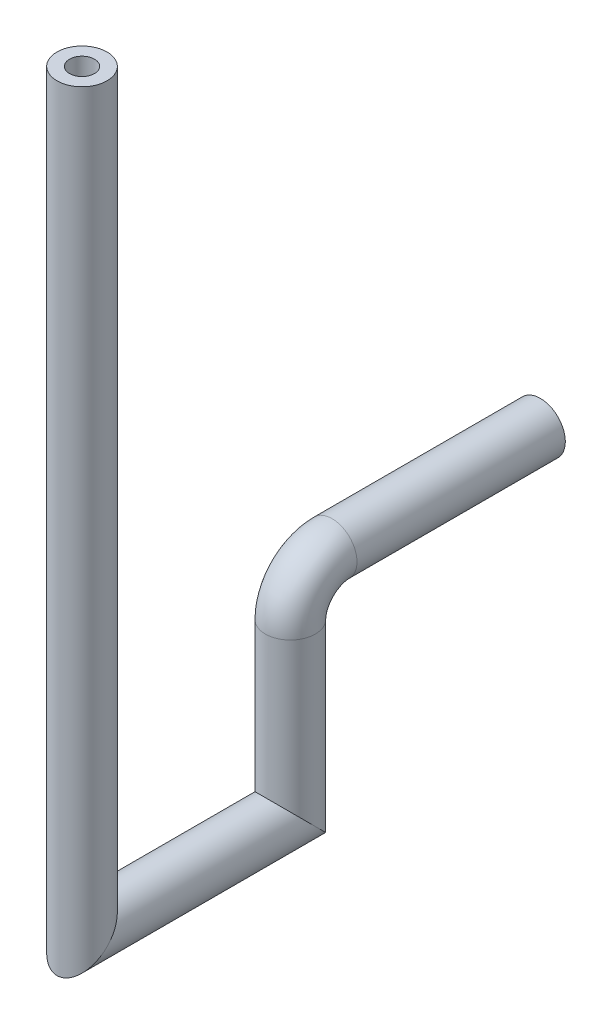
SolidWorks part; units mm, degrees
ref_plane "Plano frontal" through (0, 0, 0) normal (0, 0, 1) x (1, 0, 0)
ref_plane "Plano superior" through (0, 0, 0) normal (0, 1, 0) x (1, 0, 0)
ref_plane "Plano direito" through (0, 0, 0) normal (1, 0, 0) x (0, 0, -1)
sketch "Esboço1" plane through (0, 0, 0) normal (0, 0, 1) x (1, 0, 0)
  circle A0 centre (0, 0) radius 6
  circle A1 centre (0, 0) radius 3.5
extrude "Ressalto-extrusão1" add sketch "Esboço1" along normal blind 15
ref_plane "Plano1" through (0, 0, 15) normal (0, 0, 1) x (1, 0, 0)
sketch "Esboço2" plane through (0, 0, 15) normal (0, 0, 1) x (1, 0, 0)
  circle A0 centre (0, 0) radius 6
  circle A1 centre (0, 0) radius 3
extrude "Ressalto-extrusão2" add sketch "Esboço2" along normal blind 30
ref_plane "Plano2" through (0, 0, 45) normal (0, 0, 1) x (1, 0, 0)
sketch "Esboço3" plane through (0, 0, 45) normal (0, 0, 1) x (1, 0, 0)
  line L0 (0, -6) -> (0, 6)
  line L1 (6, 0) -> (-6, 0)
  line L2 (-6, -6) -> (6, -6)
  line L3 (-6, 0) -> (-6, -6)
  circle A0 centre (0, 0) radius 6 construction
ref_plane "Plano3" through (0, 0, 0) normal (1, 0, 0) x (0, 1, 0)
sketch "Esboço4" plane through (0, 0, 0) normal (1, 0, 0) x (0, 1, 0)
  line L0 (0, 45) -> (0, 50)
  line L1 (-6, 45) -> (6, 45) construction
  line L2 (-10, 60) -> (-50, 60)
  line L3 (-50, 60) -> (-50, 110)
  line L4 (-50, 110) -> (130, 110)
  arc A0 (-10, 60) -> (0, 50) centre (-10, 50) cw
  point P10 (0, 60)
  dimension "D2" = 10
  dimension "D1" = 15
sweep "Varredura-Fino1" add path "Esboço4" circular profile diameter 6 parameters "D1"=3, "D3"=6
ref_plane "Plano4" through (0, -6, 0) normal (0, 1, 0) x (1, 0, 0)
ref_plane "Plano5" through (0, -31, 0) normal (0, 1, 0) x (1, 0, 0)
ref_plane "Plano6" through (-6, 0, 0) normal (1, 0, 0) x (0, 0, -1)
sketch "Esboço118" plane through (0, -31, 0) normal (0, 1, 0) x (1, 0, 0)
  line L0 (-6, -60) -> (-6, -110)
  circle A0 centre (0, -110) radius 6 construction
sketch "Esboço114" plane through (-6, -37, 0) normal (1, 0, 0) x (0, -1, 0)
  line L0 (-6, -60) -> (-6, -84.5643) construction
  line L1 (-6, -60) -> (-6, -45.5701) construction
  line L2 (-6, -110) -> (-6, -131.4212) construction
  line L3 (-6.25, -60) -> (-6.25, -45.5701)
  line L4 (-6.25, -60) -> (-6.25, -84.5643)
  line L5 (-6.25, -110) -> (-6.25, -131.4212)
  line L6 (-5.75, -60) -> (-5.75, -45.5701)
  line L7 (-5.75, -60) -> (-5.75, -84.5643)
  line L8 (-5.75, -110) -> (-5.75, -131.4212)
  line L9 (-6.25, -45.5701) -> (-5.75, -45.5701)
  line L10 (-6.25, -131.4212) -> (-5.75, -131.4212)
  line L11 (-6.25, -84.5643) -> (-5.75, -84.5643)
  line L12 (-6.25, -90.4498) -> (-5.75, -90.4498)
  line L13 (-6.25, -90.4498) -> (-6.25, -110)
  line L14 (-6.25, -60) -> (-6.25, -110) construction
  line L15 (-6, -90.4498) -> (-6, -110) construction
  line L16 (-6, -60) -> (-6, -110) construction
  line L17 (-5.75, -90.4498) -> (-5.75, -110)
  line L18 (-5.75, -60) -> (-5.75, -110) construction
  line L19 (-6, -85) -> (-0.4218, -85) construction
  line L20 (-6, -60) -> (-6, -110) construction
  line L21 (-16.25, -90.4498) -> (-16.25, -110)
  line L22 (-15.75, -90.4498) -> (-15.75, -110)
  line L23 (-16.25, -90.4498) -> (-15.75, -90.4498)
  line L24 (-15.75, -110) -> (-15.75, -131.4212)
  line L25 (-16.25, -110) -> (-16.25, -131.4212)
  line L26 (-16.25, -131.4212) -> (-15.75, -131.4212)
  line L27 (-26.25, -90.4498) -> (-26.25, -110)
  line L28 (-25.75, -90.4498) -> (-25.75, -110)
  line L29 (-26.25, -90.4498) -> (-25.75, -90.4498)
  line L30 (-25.75, -110) -> (-25.75, -131.4212)
  line L31 (-26.25, -110) -> (-26.25, -131.4212)
  line L32 (-26.25, -131.4212) -> (-25.75, -131.4212)
  line L33 (-36.25, -90.4498) -> (-36.25, -110)
  line L34 (-35.75, -90.4498) -> (-35.75, -110)
  line L35 (-36.25, -90.4498) -> (-35.75, -90.4498)
  line L36 (-35.75, -110) -> (-35.75, -131.4212)
  line L37 (-36.25, -110) -> (-36.25, -131.4212)
  line L38 (-36.25, -131.4212) -> (-35.75, -131.4212)
  line L39 (-46.25, -90.4498) -> (-46.25, -110)
  line L40 (-45.75, -90.4498) -> (-45.75, -110)
  line L41 (-46.25, -90.4498) -> (-45.75, -90.4498)
  line L42 (-45.75, -110) -> (-45.75, -131.4212)
  line L43 (-46.25, -110) -> (-46.25, -131.4212)
  line L44 (-46.25, -131.4212) -> (-45.75, -131.4212)
  line L45 (-56.25, -90.4498) -> (-56.25, -110)
  line L46 (-55.75, -90.4498) -> (-55.75, -110)
  line L47 (-56.25, -90.4498) -> (-55.75, -90.4498)
  line L48 (-55.75, -110) -> (-55.75, -131.4212)
  line L49 (-56.25, -110) -> (-56.25, -131.4212)
  line L50 (-56.25, -131.4212) -> (-55.75, -131.4212)
  line L51 (-66.25, -90.4498) -> (-66.25, -110)
  line L52 (-65.75, -90.4498) -> (-65.75, -110)
  line L53 (-66.25, -90.4498) -> (-65.75, -90.4498)
  line L54 (-65.75, -110) -> (-65.75, -131.4212)
  line L55 (-66.25, -110) -> (-66.25, -131.4212)
  line L56 (-66.25, -131.4212) -> (-65.75, -131.4212)
  line L57 (-76.25, -90.4498) -> (-76.25, -110)
  line L58 (-75.75, -90.4498) -> (-75.75, -110)
  line L59 (-76.25, -90.4498) -> (-75.75, -90.4498)
  line L60 (-75.75, -110) -> (-75.75, -131.4212)
  line L61 (-76.25, -110) -> (-76.25, -131.4212)
  line L62 (-76.25, -131.4212) -> (-75.75, -131.4212)
  line L63 (-86.25, -90.4498) -> (-86.25, -110)
  line L64 (-85.75, -90.4498) -> (-85.75, -110)
  line L65 (-86.25, -90.4498) -> (-85.75, -90.4498)
  line L66 (-85.75, -110) -> (-85.75, -131.4212)
  line L67 (-86.25, -110) -> (-86.25, -131.4212)
  line L68 (-86.25, -131.4212) -> (-85.75, -131.4212)
  line L69 (-96.25, -90.4498) -> (-96.25, -110)
  line L70 (-95.75, -90.4498) -> (-95.75, -110)
  line L71 (-96.25, -90.4498) -> (-95.75, -90.4498)
  line L72 (-95.75, -110) -> (-95.75, -131.4212)
  line L73 (-96.25, -110) -> (-96.25, -131.4212)
  line L74 (-96.25, -131.4212) -> (-95.75, -131.4212)
  line L75 (-106.25, -90.4498) -> (-105.75, -90.4498)
  line L76 (-106.25, -90.4498) -> (-106.25, -110)
  line L83 (-105.75, -90.4498) -> (-105.75, -110)
  line L84 (-105.75, -110) -> (-105.75, -131.4212)
  line L85 (-106.25, -110) -> (-106.25, -131.4212)
  line L86 (-106.25, -131.4212) -> (-105.75, -131.4212)
  dimension "D4" = 2
  dimension "D1" = 0.25
  dimension "D2" = 0.25
  dimension "D3" = 10
extrude "Corte-extrusão2" cut sketch "Esboço114" along normal blind 1
ref_plane "Plano8" through (-6, 0, 0) normal (1, 0, 0) x (0, 0, -1)
sketch "Esboço119" plane through (-6, 0, 0) normal (1, 0, 0) x (0, 0, -1)
  line L0 (-108, -31.25) -> (-112, -31.25)
  line L2 (-108, -30.75) -> (-112, -30.75)
  line L3 (-112, -31.25) -> (-112, -30.75)
  line L4 (-110, -30.75) -> (-110, -31.25) construction
  line L5 (-108, -30.75) -> (-108, -31.25)
  line L6 (-112, -30.75) -> (-112, -31.25)
  line L7 (-108, -29.75) -> (-108, -30.25)
  line L8 (-108, -29.75) -> (-112, -29.75)
  line L9 (-112, -30.25) -> (-112, -29.75)
  line L10 (-108, -30.25) -> (-112, -30.25)
  line L11 (-108, -28.75) -> (-108, -29.25)
  line L12 (-108, -28.75) -> (-112, -28.75)
  line L13 (-112, -29.25) -> (-112, -28.75)
  line L14 (-108, -29.25) -> (-112, -29.25)
  line L15 (-108, -27.75) -> (-108, -28.25)
  line L16 (-108, -27.75) -> (-112, -27.75)
  line L17 (-112, -28.25) -> (-112, -27.75)
  line L18 (-108, -28.25) -> (-112, -28.25)
  line L19 (-108, -26.75) -> (-108, -27.25)
  line L20 (-108, -26.75) -> (-112, -26.75)
  line L21 (-112, -27.25) -> (-112, -26.75)
  line L22 (-108, -27.25) -> (-112, -27.25)
  line L23 (-108, -25.75) -> (-108, -26.25)
  line L24 (-108, -25.75) -> (-112, -25.75)
  line L25 (-112, -26.25) -> (-112, -25.75)
  line L26 (-108, -26.25) -> (-112, -26.25)
  line L27 (-108, -24.75) -> (-108, -25.25)
  line L28 (-108, -24.75) -> (-112, -24.75)
  line L29 (-112, -25.25) -> (-112, -24.75)
  line L30 (-108, -25.25) -> (-112, -25.25)
  line L31 (-108, -23.75) -> (-108, -24.25)
  line L32 (-108, -23.75) -> (-112, -23.75)
  line L33 (-112, -24.25) -> (-112, -23.75)
  line L34 (-108, -24.25) -> (-112, -24.25)
  line L35 (-108, -22.75) -> (-108, -23.25)
  line L36 (-108, -22.75) -> (-112, -22.75)
  line L37 (-112, -23.25) -> (-112, -22.75)
  line L38 (-108, -23.25) -> (-112, -23.25)
  line L39 (-108, -21.75) -> (-108, -22.25)
  line L40 (-108, -21.75) -> (-112, -21.75)
  line L41 (-112, -22.25) -> (-112, -21.75)
  line L42 (-108, -22.25) -> (-112, -22.25)
  line L43 (-108, -20.75) -> (-108, -21.25)
  line L44 (-108, -20.75) -> (-112, -20.75)
  line L45 (-112, -21.25) -> (-112, -20.75)
  line L46 (-108, -21.25) -> (-112, -21.25)
  line L47 (-108, -19.75) -> (-108, -20.25)
  line L48 (-108, -19.75) -> (-112, -19.75)
  line L49 (-112, -20.25) -> (-112, -19.75)
  line L50 (-108, -20.25) -> (-112, -20.25)
  line L51 (-108, -18.75) -> (-108, -19.25)
  line L52 (-108, -18.75) -> (-112, -18.75)
  line L53 (-112, -19.25) -> (-112, -18.75)
  line L54 (-108, -19.25) -> (-112, -19.25)
  line L55 (-108, -17.75) -> (-108, -18.25)
  line L56 (-108, -17.75) -> (-112, -17.75)
  line L57 (-112, -18.25) -> (-112, -17.75)
  line L58 (-108, -18.25) -> (-112, -18.25)
  line L59 (-108, -16.75) -> (-108, -17.25)
  line L60 (-108, -16.75) -> (-112, -16.75)
  line L61 (-112, -17.25) -> (-112, -16.75)
  line L62 (-108, -17.25) -> (-112, -17.25)
  line L63 (-108, -15.75) -> (-108, -16.25)
  line L64 (-108, -15.75) -> (-112, -15.75)
  line L65 (-112, -16.25) -> (-112, -15.75)
  line L66 (-108, -16.25) -> (-112, -16.25)
  line L67 (-108, -14.75) -> (-108, -15.25)
  line L68 (-108, -14.75) -> (-112, -14.75)
  line L69 (-112, -15.25) -> (-112, -14.75)
  line L70 (-108, -15.25) -> (-112, -15.25)
  line L71 (-108, -13.75) -> (-108, -14.25)
  line L72 (-108, -13.75) -> (-112, -13.75)
  line L73 (-112, -14.25) -> (-112, -13.75)
  line L74 (-108, -14.25) -> (-112, -14.25)
  line L75 (-108, -12.75) -> (-108, -13.25)
  line L76 (-108, -12.75) -> (-112, -12.75)
  line L77 (-112, -13.25) -> (-112, -12.75)
  line L78 (-108, -13.25) -> (-112, -13.25)
  line L79 (-108, -11.75) -> (-108, -12.25)
  line L80 (-108, -11.75) -> (-112, -11.75)
  line L81 (-112, -12.25) -> (-112, -11.75)
  line L82 (-108, -12.25) -> (-112, -12.25)
  line L83 (-108, -10.75) -> (-108, -11.25)
  line L84 (-108, -10.75) -> (-112, -10.75)
  line L85 (-112, -11.25) -> (-112, -10.75)
  line L86 (-108, -11.25) -> (-112, -11.25)
  line L87 (-108, -9.75) -> (-108, -10.25)
  line L88 (-108, -9.75) -> (-112, -9.75)
  line L89 (-112, -10.25) -> (-112, -9.75)
  line L90 (-108, -10.25) -> (-112, -10.25)
  line L91 (-108, -8.75) -> (-108, -9.25)
  line L92 (-108, -8.75) -> (-112, -8.75)
  line L93 (-112, -9.25) -> (-112, -8.75)
  line L94 (-108, -9.25) -> (-112, -9.25)
  line L95 (-108, -7.75) -> (-108, -8.25)
  line L96 (-108, -7.75) -> (-112, -7.75)
  line L97 (-112, -8.25) -> (-112, -7.75)
  line L98 (-108, -8.25) -> (-112, -8.25)
  line L99 (-108, -6.75) -> (-108, -7.25)
  line L100 (-108, -6.75) -> (-112, -6.75)
  line L101 (-112, -7.25) -> (-112, -6.75)
  line L102 (-108, -7.25) -> (-112, -7.25)
  line L103 (-108, -5.75) -> (-108, -6.25)
  line L104 (-108, -5.75) -> (-112, -5.75)
  line L105 (-112, -6.25) -> (-112, -5.75)
  line L106 (-108, -6.25) -> (-112, -6.25)
  line L107 (-108, -4.75) -> (-108, -5.25)
  line L108 (-108, -4.75) -> (-112, -4.75)
  line L109 (-112, -5.25) -> (-112, -4.75)
  line L110 (-108, -5.25) -> (-112, -5.25)
  line L111 (-108, -3.75) -> (-108, -4.25)
  line L112 (-108, -3.75) -> (-112, -3.75)
  line L113 (-112, -4.25) -> (-112, -3.75)
  line L114 (-108, -4.25) -> (-112, -4.25)
  line L115 (-108, -2.75) -> (-108, -3.25)
  line L116 (-108, -2.75) -> (-112, -2.75)
  line L117 (-112, -3.25) -> (-112, -2.75)
  line L118 (-108, -3.25) -> (-112, -3.25)
  line L119 (-108, -1.75) -> (-108, -2.25)
  line L120 (-108, -1.75) -> (-112, -1.75)
  line L121 (-112, -2.25) -> (-112, -1.75)
  line L122 (-108, -2.25) -> (-112, -2.25)
  line L123 (-108, -0.75) -> (-108, -1.25)
  line L124 (-108, -0.75) -> (-112, -0.75)
  line L125 (-112, -1.25) -> (-112, -0.75)
  line L126 (-108, -1.25) -> (-112, -1.25)
  line L127 (-108, 0.25) -> (-108, -0.25)
  line L128 (-108, 0.25) -> (-112, 0.25)
  line L129 (-112, -0.25) -> (-112, 0.25)
  line L130 (-108, -0.25) -> (-112, -0.25)
  line L131 (-108, 1.25) -> (-108, 0.75)
  line L132 (-108, 1.25) -> (-112, 1.25)
  line L133 (-112, 0.75) -> (-112, 1.25)
  line L134 (-108, 0.75) -> (-112, 0.75)
  line L135 (-108, 2.25) -> (-108, 1.75)
  line L136 (-108, 2.25) -> (-112, 2.25)
  line L137 (-112, 1.75) -> (-112, 2.25)
  line L138 (-108, 1.75) -> (-112, 1.75)
  line L139 (-108, 3.25) -> (-108, 2.75)
  line L140 (-108, 3.25) -> (-112, 3.25)
  line L141 (-112, 2.75) -> (-112, 3.25)
  line L142 (-108, 2.75) -> (-112, 2.75)
  line L143 (-108, 4.25) -> (-108, 3.75)
  line L144 (-108, 4.25) -> (-112, 4.25)
  line L145 (-112, 3.75) -> (-112, 4.25)
  line L146 (-108, 3.75) -> (-112, 3.75)
  line L147 (-108, 5.25) -> (-108, 4.75)
  line L148 (-108, 5.25) -> (-112, 5.25)
  line L149 (-112, 4.75) -> (-112, 5.25)
  line L150 (-108, 4.75) -> (-112, 4.75)
  line L151 (-108, 6.25) -> (-108, 5.75)
  line L152 (-108, 6.25) -> (-112, 6.25)
  line L153 (-112, 5.75) -> (-112, 6.25)
  line L154 (-108, 5.75) -> (-112, 5.75)
  line L155 (-108, 7.25) -> (-108, 6.75)
  line L156 (-108, 7.25) -> (-112, 7.25)
  line L157 (-112, 6.75) -> (-112, 7.25)
  line L158 (-108, 6.75) -> (-112, 6.75)
  line L159 (-108, 8.25) -> (-108, 7.75)
  line L160 (-108, 8.25) -> (-112, 8.25)
  line L161 (-112, 7.75) -> (-112, 8.25)
  line L162 (-108, 7.75) -> (-112, 7.75)
  line L163 (-108, 9.25) -> (-108, 8.75)
  line L164 (-108, 9.25) -> (-112, 9.25)
  line L165 (-112, 8.75) -> (-112, 9.25)
  line L166 (-108, 8.75) -> (-112, 8.75)
  line L167 (-108, 10.25) -> (-108, 9.75)
  line L168 (-108, 10.25) -> (-112, 10.25)
  line L169 (-112, 9.75) -> (-112, 10.25)
  line L170 (-108, 9.75) -> (-112, 9.75)
  line L171 (-108, 11.25) -> (-108, 10.75)
  line L172 (-108, 11.25) -> (-112, 11.25)
  line L173 (-112, 10.75) -> (-112, 11.25)
  line L174 (-108, 10.75) -> (-112, 10.75)
  line L175 (-108, 12.25) -> (-108, 11.75)
  line L176 (-108, 12.25) -> (-112, 12.25)
  line L177 (-112, 11.75) -> (-112, 12.25)
  line L178 (-108, 11.75) -> (-112, 11.75)
  line L179 (-108, 13.25) -> (-108, 12.75)
  line L180 (-108, 13.25) -> (-112, 13.25)
  line L181 (-112, 12.75) -> (-112, 13.25)
  line L182 (-108, 12.75) -> (-112, 12.75)
  line L183 (-108, 14.25) -> (-108, 13.75)
  line L184 (-108, 14.25) -> (-112, 14.25)
  line L185 (-112, 13.75) -> (-112, 14.25)
  line L186 (-108, 13.75) -> (-112, 13.75)
  line L187 (-108, 15.25) -> (-108, 14.75)
  line L188 (-108, 15.25) -> (-112, 15.25)
  line L189 (-112, 14.75) -> (-112, 15.25)
  line L190 (-108, 14.75) -> (-112, 14.75)
  line L191 (-108, 16.25) -> (-108, 15.75)
  line L192 (-108, 16.25) -> (-112, 16.25)
  line L193 (-112, 15.75) -> (-112, 16.25)
  line L194 (-108, 15.75) -> (-112, 15.75)
  line L195 (-108, 17.25) -> (-108, 16.75)
  line L196 (-108, 17.25) -> (-112, 17.25)
  line L197 (-112, 16.75) -> (-112, 17.25)
  line L198 (-108, 16.75) -> (-112, 16.75)
  line L199 (-108, 18.25) -> (-108, 17.75)
  line L200 (-108, 18.25) -> (-112, 18.25)
  line L201 (-112, 17.75) -> (-112, 18.25)
  line L202 (-108, 17.75) -> (-112, 17.75)
  line L203 (-108, 19.25) -> (-108, 18.75)
  line L204 (-108, 19.25) -> (-112, 19.25)
  line L205 (-112, 18.75) -> (-112, 19.25)
  line L206 (-108, 18.75) -> (-112, 18.75)
  line L207 (-108, 20.25) -> (-108, 19.75)
  line L208 (-108, 20.25) -> (-112, 20.25)
  line L209 (-112, 19.75) -> (-112, 20.25)
  line L210 (-108, 19.75) -> (-112, 19.75)
  line L211 (-108, 21.25) -> (-108, 20.75)
  line L212 (-108, 21.25) -> (-112, 21.25)
  line L213 (-112, 20.75) -> (-112, 21.25)
  line L214 (-108, 20.75) -> (-112, 20.75)
  line L215 (-108, 22.25) -> (-108, 21.75)
  line L216 (-108, 22.25) -> (-112, 22.25)
  line L217 (-112, 21.75) -> (-112, 22.25)
  line L218 (-108, 21.75) -> (-112, 21.75)
  line L219 (-108, 23.25) -> (-108, 22.75)
  line L220 (-108, 23.25) -> (-112, 23.25)
  line L221 (-112, 22.75) -> (-112, 23.25)
  line L222 (-108, 22.75) -> (-112, 22.75)
  line L223 (-108, 24.25) -> (-108, 23.75)
  line L224 (-108, 24.25) -> (-112, 24.25)
  line L225 (-112, 23.75) -> (-112, 24.25)
  line L226 (-108, 23.75) -> (-112, 23.75)
  line L227 (-108, 25.25) -> (-108, 24.75)
  line L228 (-108, 25.25) -> (-112, 25.25)
  line L229 (-112, 24.75) -> (-112, 25.25)
  line L230 (-108, 24.75) -> (-112, 24.75)
  line L231 (-108, 26.25) -> (-108, 25.75)
  line L232 (-108, 26.25) -> (-112, 26.25)
  line L233 (-112, 25.75) -> (-112, 26.25)
  line L234 (-108, 25.75) -> (-112, 25.75)
  line L235 (-108, 27.25) -> (-108, 26.75)
  line L236 (-108, 27.25) -> (-112, 27.25)
  line L237 (-112, 26.75) -> (-112, 27.25)
  line L238 (-108, 26.75) -> (-112, 26.75)
  line L239 (-108, 28.25) -> (-108, 27.75)
  line L240 (-108, 28.25) -> (-112, 28.25)
  line L241 (-112, 27.75) -> (-112, 28.25)
  line L242 (-108, 27.75) -> (-112, 27.75)
  line L243 (-108, 29.25) -> (-108, 28.75)
  line L244 (-108, 29.25) -> (-112, 29.25)
  line L245 (-112, 28.75) -> (-112, 29.25)
  line L246 (-108, 28.75) -> (-112, 28.75)
  line L247 (-108, 30.25) -> (-108, 29.75)
  line L248 (-108, 30.25) -> (-112, 30.25)
  line L249 (-112, 29.75) -> (-112, 30.25)
  line L250 (-108, 29.75) -> (-112, 29.75)
  line L251 (-108, 31.25) -> (-108, 30.75)
  line L252 (-108, 31.25) -> (-112, 31.25)
  line L253 (-112, 30.75) -> (-112, 31.25)
  line L254 (-108, 30.75) -> (-112, 30.75)
  line L255 (-108, 32.25) -> (-108, 31.75)
  line L256 (-108, 32.25) -> (-112, 32.25)
  line L257 (-112, 31.75) -> (-112, 32.25)
  line L258 (-108, 31.75) -> (-112, 31.75)
  line L259 (-108, 33.25) -> (-108, 32.75)
  line L260 (-108, 33.25) -> (-112, 33.25)
  line L261 (-112, 32.75) -> (-112, 33.25)
  line L262 (-108, 32.75) -> (-112, 32.75)
  line L263 (-108, 34.25) -> (-108, 33.75)
  line L264 (-108, 34.25) -> (-112, 34.25)
  line L265 (-112, 33.75) -> (-112, 34.25)
  line L266 (-108, 33.75) -> (-112, 33.75)
  line L267 (-108, 35.25) -> (-108, 34.75)
  line L268 (-108, 35.25) -> (-112, 35.25)
  line L269 (-112, 34.75) -> (-112, 35.25)
  line L270 (-108, 34.75) -> (-112, 34.75)
  line L271 (-108, 36.25) -> (-108, 35.75)
  line L272 (-108, 36.25) -> (-112, 36.25)
  line L273 (-112, 35.75) -> (-112, 36.25)
  line L274 (-108, 35.75) -> (-112, 35.75)
  line L275 (-108, 37.25) -> (-108, 36.75)
  line L276 (-108, 37.25) -> (-112, 37.25)
  line L277 (-112, 36.75) -> (-112, 37.25)
  line L278 (-108, 36.75) -> (-112, 36.75)
  line L279 (-108, 38.25) -> (-108, 37.75)
  line L280 (-108, 38.25) -> (-112, 38.25)
  line L281 (-112, 37.75) -> (-112, 38.25)
  line L282 (-108, 37.75) -> (-112, 37.75)
  line L283 (-108, 39.25) -> (-108, 38.75)
  line L284 (-108, 39.25) -> (-112, 39.25)
  line L285 (-112, 38.75) -> (-112, 39.25)
  line L286 (-108, 38.75) -> (-112, 38.75)
  line L287 (-108, 40.25) -> (-108, 39.75)
  line L288 (-108, 40.25) -> (-112, 40.25)
  line L289 (-112, 39.75) -> (-112, 40.25)
  line L290 (-108, 39.75) -> (-112, 39.75)
  line L291 (-108, 41.25) -> (-108, 40.75)
  line L292 (-108, 41.25) -> (-112, 41.25)
  line L293 (-112, 40.75) -> (-112, 41.25)
  line L294 (-108, 40.75) -> (-112, 40.75)
  line L295 (-108, 42.25) -> (-108, 41.75)
  line L296 (-108, 42.25) -> (-112, 42.25)
  line L297 (-112, 41.75) -> (-112, 42.25)
  line L298 (-108, 41.75) -> (-112, 41.75)
  line L299 (-108, 43.25) -> (-108, 42.75)
  line L300 (-108, 43.25) -> (-112, 43.25)
  line L301 (-112, 42.75) -> (-112, 43.25)
  line L302 (-108, 42.75) -> (-112, 42.75)
  line L303 (-108, 44.25) -> (-108, 43.75)
  line L304 (-108, 44.25) -> (-112, 44.25)
  line L305 (-112, 43.75) -> (-112, 44.25)
  line L306 (-108, 43.75) -> (-112, 43.75)
  line L307 (-108, 45.25) -> (-108, 44.75)
  line L308 (-108, 45.25) -> (-112, 45.25)
  line L309 (-112, 44.75) -> (-112, 45.25)
  line L310 (-108, 44.75) -> (-112, 44.75)
  line L311 (-108, 46.25) -> (-108, 45.75)
  line L312 (-108, 46.25) -> (-112, 46.25)
  line L313 (-112, 45.75) -> (-112, 46.25)
  line L314 (-108, 45.75) -> (-112, 45.75)
  line L315 (-108, 47.25) -> (-108, 46.75)
  line L316 (-108, 47.25) -> (-112, 47.25)
  line L317 (-112, 46.75) -> (-112, 47.25)
  line L318 (-108, 46.75) -> (-112, 46.75)
  line L319 (-108, 48.25) -> (-108, 47.75)
  line L320 (-108, 48.25) -> (-112, 48.25)
  line L321 (-112, 47.75) -> (-112, 48.25)
  line L322 (-108, 47.75) -> (-112, 47.75)
  line L323 (-108, 49.25) -> (-108, 48.75)
  line L324 (-108, 49.25) -> (-112, 49.25)
  line L325 (-112, 48.75) -> (-112, 49.25)
  line L326 (-108, 48.75) -> (-112, 48.75)
  line L327 (-108, 50.25) -> (-108, 49.75)
  line L328 (-108, 50.25) -> (-112, 50.25)
  line L329 (-112, 49.75) -> (-112, 50.25)
  line L330 (-108, 49.75) -> (-112, 49.75)
  line L331 (-108, 51.25) -> (-108, 50.75)
  line L332 (-108, 51.25) -> (-112, 51.25)
  line L333 (-112, 50.75) -> (-112, 51.25)
  line L334 (-108, 50.75) -> (-112, 50.75)
  line L335 (-108, 52.25) -> (-108, 51.75)
  line L336 (-108, 52.25) -> (-112, 52.25)
  line L337 (-112, 51.75) -> (-112, 52.25)
  line L338 (-108, 51.75) -> (-112, 51.75)
  line L339 (-108, 53.25) -> (-108, 52.75)
  line L340 (-108, 53.25) -> (-112, 53.25)
  line L341 (-112, 52.75) -> (-112, 53.25)
  line L342 (-108, 52.75) -> (-112, 52.75)
  line L343 (-108, 54.25) -> (-108, 53.75)
  line L344 (-108, 54.25) -> (-112, 54.25)
  line L345 (-112, 53.75) -> (-112, 54.25)
  line L346 (-108, 53.75) -> (-112, 53.75)
  line L347 (-108, 55.25) -> (-108, 54.75)
  line L348 (-108, 55.25) -> (-112, 55.25)
  line L349 (-112, 54.75) -> (-112, 55.25)
  line L350 (-108, 54.75) -> (-112, 54.75)
  line L351 (-108, 56.25) -> (-108, 55.75)
  line L352 (-108, 56.25) -> (-112, 56.25)
  line L353 (-112, 55.75) -> (-112, 56.25)
  line L354 (-108, 55.75) -> (-112, 55.75)
  line L355 (-108, 57.25) -> (-108, 56.75)
  line L356 (-108, 57.25) -> (-112, 57.25)
  line L357 (-112, 56.75) -> (-112, 57.25)
  line L358 (-108, 56.75) -> (-112, 56.75)
  line L359 (-108, 58.25) -> (-108, 57.75)
  line L360 (-108, 58.25) -> (-112, 58.25)
  line L361 (-112, 57.75) -> (-112, 58.25)
  line L362 (-108, 57.75) -> (-112, 57.75)
  line L363 (-108, 59.25) -> (-108, 58.75)
  line L364 (-108, 59.25) -> (-112, 59.25)
  line L365 (-112, 58.75) -> (-112, 59.25)
  line L366 (-108, 58.75) -> (-112, 58.75)
  line L367 (-108, 59.75) -> (-112, 59.75)
  line L368 (-108, 60.25) -> (-112, 60.25)
  line L369 (-108, 60.25) -> (-108, 59.75)
  line L370 (-112, 59.75) -> (-112, 60.25)
  line L371 (-108, 60.75) -> (-112, 60.75)
  line L372 (-108, 61.25) -> (-112, 61.25)
  line L373 (-108, 61.25) -> (-108, 60.75)
  line L374 (-112, 60.75) -> (-112, 61.25)
  line L375 (-108, 61.75) -> (-112, 61.75)
  line L376 (-108, 62.25) -> (-112, 62.25)
  line L377 (-108, 62.25) -> (-108, 61.75)
  line L378 (-112, 61.75) -> (-112, 62.25)
  line L379 (-108, 62.75) -> (-112, 62.75)
  line L380 (-108, 63.25) -> (-112, 63.25)
  line L381 (-108, 63.25) -> (-108, 62.75)
  line L382 (-112, 62.75) -> (-112, 63.25)
  line L383 (-108, 63.75) -> (-112, 63.75)
  line L384 (-108, 64.25) -> (-112, 64.25)
  line L385 (-108, 64.25) -> (-108, 63.75)
  line L386 (-112, 63.75) -> (-112, 64.25)
  line L387 (-108, 64.75) -> (-112, 64.75)
  line L388 (-108, 65.25) -> (-112, 65.25)
  line L389 (-108, 65.25) -> (-108, 64.75)
  line L390 (-112, 64.75) -> (-112, 65.25)
  line L391 (-108, 65.75) -> (-112, 65.75)
  line L392 (-108, 66.25) -> (-112, 66.25)
  line L393 (-108, 66.25) -> (-108, 65.75)
  line L394 (-112, 65.75) -> (-112, 66.25)
  line L395 (-108, 66.75) -> (-112, 66.75)
  line L396 (-108, 67.25) -> (-112, 67.25)
  line L397 (-108, 67.25) -> (-108, 66.75)
  line L398 (-112, 66.75) -> (-112, 67.25)
  line L399 (-108, 67.75) -> (-112, 67.75)
  line L400 (-108, 68.25) -> (-112, 68.25)
  line L401 (-108, 68.25) -> (-108, 67.75)
  line L402 (-112, 67.75) -> (-112, 68.25)
  line L403 (-108, 68.75) -> (-112, 68.75)
  line L404 (-108, 69.25) -> (-112, 69.25)
  line L405 (-108, 69.25) -> (-108, 68.75)
  line L406 (-112, 68.75) -> (-112, 69.25)
  dimension "D1" = 91
  dimension "D2" = 2
  dimension "D3" = 2
  dimension "D4" = 11
extrude "Corte-extrusão3" cut sketch "Esboço119" along normal blind 0.5 contours L366 L363 L364 L365 | L362 L359 L360 L361 | L358 L355 L356 L357 | L354 L351 L352 L353 | L350 L347 L348 L349 | L346 L343 L344 L345 | L342 L339 L340 L341 | L338 L335 L336 L337 | L334 L331 L332 L333 | L330 L327 L328 L329 | L326 L323 L324 L325 | L322 L319 L320 L321 | L318 L315 L316 L317 | L314 L311 L312 L313 | L310 L307 L308 L309 | L306 L303 L304 L305 | L302 L299 L300 L301 | L298 L295 L296 L297 | L294 L291 L292 L293 | L290 L287 L288 L289 | L286 L283 L284 L285 | L282 L279 L280 L281 | L278 L275 L276 L277 | L274 L271 L272 L273 | L270 L267 L268 L269 | L266 L263 L264 L265 | L262 L259 L260 L261 | L258 L255 L256 L257 | L254 L251 L252 L253 | L250 L247 L248 L249 | L246 L243 L244 L245 | L242 L239 L240 L241 | L238 L235 L236 L237 | L234 L231 L232 L233 | L230 L227 L228 L229 | L226 L223 L224 L225 | L222 L219 L220 L221 | L218 L215 L216 L217 | L214 L211 L212 L213 | L210 L207 L208 L209 | L206 L203 L204 L205 | L202 L199 L200 L201 | L198 L195 L196 L197 | L194 L191 L192 L193 | L190 L187 L188 L189 | L186 L183 L184 L185 | L182 L179 L180 L181 | L178 L175 L176 L177 | L174 L171 L172 L173 | L170 L167 L168 L169 | L166 L163 L164 L165 | L162 L159 L160 L161 | L158 L155 L156 L157 | L154 L151 L152 L153 | L150 L147 L148 L149 | L142 L139 L140 L141 | L138 L135 L136 L137 | L134 L131 L132 L133 | L130 L127 L128 L129 | L126 L123 L124 L125 | L122 L119 L120 L121 | L118 L115 L116 L117 | L114 L111 L112 L113 | L110 L107 L108 L109 | L106 L103 L104 L105 | L102 L99 L100 L101 | L98 L95 L96 L97 | L94 L91 L92 L93 | L90 L87 L88 L89 | L82 L79 L80 L81 | L78 L75 L76 L77 | L74 L71 L72 L73 | L70 L67 L68 L69 | L66 L63 L64 L65 | L62 L59 L60 L61 | L58 L55 L56 L57 | L54 L51 L52 L53 | L50 L47 L48 L49 | L46 L43 L44 L45 | L42 L39 L40 L41 | L38 L35 L36 L37 | L34 L31 L32 L33 | L30 L27 L28 L29 | L26 L23 L24 L25 | L22 L19 L20 L21 | L18 L15 L16 L17 | L14 L11 L12 L13 | L10 L7 L8 L9 | L4 L2 L3 L0 | L2 L4 L0 L5 | L370 L367 L369 L368 | L374 L371 L373 L372 | L378 L375 L377 L376 | L382 L379 L381 L380 | L386 L383 L385 L384 | L390 L387 L389 L388 | L394 L391 L393 L392 | L398 L395 L397 L396 | L402 L399 L401 L400 | L406 L403 L405 L404 | L144 L145 L146 L143 | L86 L85 L84 L83 region at (-6, -31, 109) region at (-6, -31, 111) region at (-6, -30, 110) region at (-6, -29, 110) region at (-6, -28, 110) region at (-6, -27, 110) region at (-6, -26, 110) region at (-6, -25, 110) region at (-6, -24, 110) region at (-6, -23, 110) region at (-6, -22, 110) region at (-6, -21, 110) region at (-6, -20, 110) region at (-6, -19, 110) region at (-6, -18, 110) region at (-6, -17, 110) region at (-6, -16, 110) region at (-6, -15, 110) region at (-6, -14, 110) region at (-6, -13, 110) region at (-6, -12, 110) region at (-6, -10, 110) region at (-6, -9, 110) region at (-6, -8, 110) region at (-6, -7, 110) region at (-6, -6, 110) region at (-6, -5, 110) region at (-6, -4, 110) region at (-6, -3, 110) region at (-6, -2, 110) region at (-6, -1, 110) region at (-6, 0, 110) region at (-6, 1, 110) region at (-6, 2, 110) region at (-6, 3, 110) region at (-6, 5, 110) region at (-6, 6, 110) region at (-6, 7, 110) region at (-6, 8, 110) region at (-6, 9, 110) region at (-6, 10, 110) region at (-6, 11, 110) region at (-6, 12, 110) region at (-6, 13, 110) region at (-6, 14, 110) region at (-6, 15, 110) region at (-6, 16, 110) region at (-6, 17, 110) region at (-6, 18, 110) region at (-6, 19, 110) region at (-6, 20, 110) region at (-6, 21, 110) region at (-6, 22, 110) region at (-6, 23, 110) region at (-6, 24, 110) region at (-6, 25, 110) region at (-6, 26, 110) region at (-6, 27, 110) region at (-6, 28, 110) region at (-6, 29, 110)
